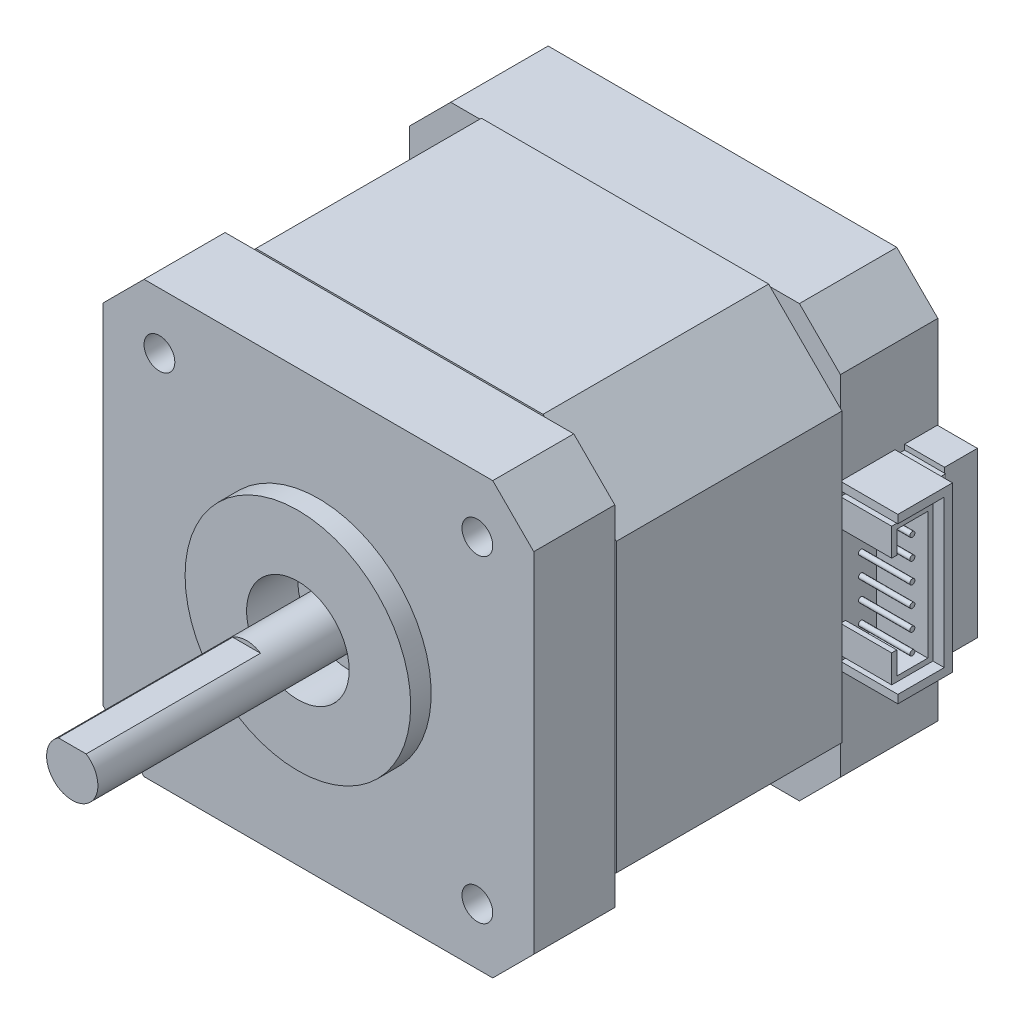
SolidWorks part; units mm, degrees
ref_plane "Front Plane" through (0, 0, 0) normal (0, 0, 1) x (1, 0, 0)
ref_plane "Top Plane" through (0, 0, 0) normal (0, 1, 0) x (1, 0, 0)
ref_plane "Right Plane" through (0, 0, 0) normal (1, 0, 0) x (0, 0, -1)
sketch "Sketch1" plane through (0, 0, 0) normal (0, 0, 1) x (1, 0, 0)
  line L0 (-17, 21) -> (-21, 17)
  line L1 (-17, -21) -> (17, -21)
  line L2 (-21, -17) -> (-21, 17)
  line L3 (-17, 21) -> (17, 21)
  line L4 (21, -17) -> (21, 17)
  line L5 (21, 17) -> (17, 21)
  line L6 (17, -21) -> (21, -17)
  line L12 (-21, -17) -> (-17, -21)
  point P0 (0, 0)
  point P15 (0, 0)
  dimension "D1" = 4
extrude "Boss-Extrude1" add sketch "Sketch1" along normal blind 9.5
sketch "Sketch2" plane through (0, 0, 9.5) normal (0, 0, 1) x (1, 0, 0)
  line L0 (14, 21.15) -> (21.15, 14)
  line L5 (-14, -21.15) -> (14, -21.15)
  line L6 (-21.15, -14) -> (-21.15, 14)
  line L7 (-14, 21.15) -> (14, 21.15)
  line L12 (21.15, -14) -> (21.15, 14)
  line L14 (17.5, -17.5) -> (17.575, -17.575) construction
  line L15 (-21.15, 14) -> (-14, 21.15)
  line L16 (21.15, -14) -> (14, -21.15)
  line L17 (-14, -21.15) -> (-21.15, -14)
  line L18 (17.5, 17.5) -> (17.575, 17.575) construction
  point P0 (0, 0)
  point P1 (0, 0)
  point P13 (0, 0)
  point P16 (0, 0)
  point P19 (0, 0)
  point P22 (0, 0)
  point P29 (0, 0)
  dimension "D1" = 4
  dimension "D5" = 4
extrude "Boss-Extrude2" add sketch "Sketch2" along normal blind 22
sketch "Sketch3" plane through (0, 0, 31.5) normal (0, 0, 1) x (1, 0, 0)
  line L0 (-17, 21) -> (17, 21)
  line L1 (17, 21) -> (21, 17)
  line L2 (21, 17) -> (21, -17)
  line L3 (21, -17) -> (17, -21)
  line L4 (17, -21) -> (-17, -21)
  line L5 (-17, -21) -> (-21, -17)
  line L6 (-21, -17) -> (-21, 17)
  line L7 (-21, 17) -> (-17, 21)
extrude "Boss-Extrude3" add sketch "Sketch3" along normal blind 7.9
sketch "Sketch5" plane through (0, 0, 39.4) normal (0, 0, 1) x (1, 0, 0)
  circle A0 centre (0, 0) radius 11
  circle A1 centre (0, 0) radius 5
  dimension "D1" = 22
  dimension "D2" = 10
extrude "Boss-Extrude4" add sketch "Sketch5" along normal blind 2
sketch "Sketch6" plane through (0, 0, 39.4) normal (0, 0, 1) x (1, 0, 0)
  circle A0 centre (0, 0) radius 5
extrude "Cut-Extrude1" cut sketch "Sketch6" against normal blind 3
sketch "Sketch7" plane through (0, 0, 36.4) normal (0, 0, 1) x (1, 0, 0)
  circle A0 centre (0, 0) radius 2.5
  dimension "D1" = 5
extrude "Boss-Extrude5" add sketch "Sketch7" along normal up to surface (5 mm away) up to face at (11, 0, 41.4)
sketch "Sketch8" plane through (0, 0, 41.4) normal (0, 0, 1) x (1, 0, 0)
  circle A0 centre (0, 0) radius 2.5
extrude "Boss-Extrude6" add sketch "Sketch8" along normal blind 22
sketch "Sketch9" plane through (0, 0, 63.4) normal (0, 0, 1) x (1, 0, 0)
  line L0 (-2.3166, 2.1) -> (3.6979, 2.1)
  line L1 (3.6979, 2.1) -> (-0.1236, 3.991)
  line L2 (-0.1236, 3.991) -> (-2.3166, 2.1)
extrude "Cut-Extrude2" cut sketch "Sketch9" against normal blind 17
sketch "Sketch10" plane through (0, 21.15, 0) normal (0, 1, 0) x (1, 0, 0)
  line L1 (-13, -13.6909) -> (13, -13.6909)
  line L3 (-13, -27.8113) -> (13, -27.8113)
  line L6 (-13, -13.6909) -> (-13, -27.8113)
  line L8 (13, -13.6909) -> (13, -27.8113)
extrude "Boss-Extrude7" [suppressed] add sketch "Sketch10" along normal blind 0.01
sketch "Sketch11" plane through (21, 0, 0) normal (1, 0, 0) x (0, 0, -1)
  line L1 (-3.2456, -8) -> (-0.0456, -8)
  line L3 (-3.2456, 8) -> (-0.0456, 8)
  line L5 (-3.2456, 8) -> (-3.2456, -8)
  line L7 (-0.0456, 8) -> (-0.0456, -8)
  point P0 (0, 0)
  dimension "D2" = 3.2
extrude "Boss-Extrude8" add sketch "Sketch11" along normal blind 3.9
sketch "Sketch12" plane through (21, 0, 0) normal (1, 0, 0) x (0, 0, -1)
  line L0 (-9.5, -14.15) -> (-9.5, 14.15) construction
  line L2 (-9.5, 7.479) -> (-9.5, 7.2)
  line L5 (-0.0456, 8) -> (-3.2456, 8) construction
  line L6 (-9.5, 7.2) -> (-4.9761, 7.2)
  line L9 (-4.1761, 7.2) -> (-4.1761, -7.2)
  line L10 (-4.1761, 8) -> (-9.5, 8)
  line L11 (-9.5, -14) -> (-9.5, 14) construction
  line L12 (-9.5, 7.479) -> (-9.5, 7.2)
  line L13 (-0.0456, 0) -> (6.3047, 0) construction
  line L14 (-0.0456, -8) -> (-0.0456, 8) construction
  line L15 (-9.5, -7.2) -> (-4.9761, -7.2)
  line L16 (-9.5, 7.2) -> (-9.5, 8)
  line L17 (-9.5, -7.2) -> (-9.5, -8)
  line L19 (-4.1761, -8) -> (-9.5, -8)
  line L20 (-4.9761, 7.2) -> (-4.9761, -7.2)
  line L21 (-4.1761, 8) -> (-4.1761, 7.2)
  line L22 (-4.1761, -7.2) -> (-4.1761, -8)
  dimension "D1" = 0.8
  dimension "D2" = 0.8
extrude "Boss-Extrude9" add sketch "Sketch12" along normal blind 5.6 contours L16 L10 L21 L9 L22 L19 L17 L15 L20 L6
sketch "Sketch13" plane through (21, 0, 0) normal (1, 0, 0) x (0, 0, -1)
  line L0 (-4.1761, 8) -> (-4.1761, -8) construction
  line L1 (-4.1761, 7.5) -> (-3.2456, 7.5)
  line L2 (-4.1761, 7.5) -> (-4.1761, -7.5)
  line L3 (-4.1761, -7.5) -> (-3.2456, -7.5)
  line L4 (-3.2456, 7.5) -> (-3.2456, -7.5)
  line L5 (-3.2456, 8) -> (-3.2456, -8) construction
  line L6 (-0.0456, 8) -> (-3.2456, 8) construction
  line L7 (-3.2456, -8) -> (-0.0456, -8) construction
  dimension "D1" = 0.5
  dimension "D2" = 0.5
extrude "Boss-Extrude10" add sketch "Sketch13" along normal up to surface (3.9 mm away) up to face at (24.9, 0, 1.6456)
sketch "Sketch14" plane through (24.9, 0, 0) normal (1, 0, 0) x (0, 0, -1)
  line L1 (-4.1761, 7.5) -> (-3.2456, 7.5)
  line L2 (-4.1761, 7.5) -> (-4.1761, -7.5)
  line L3 (-4.1761, -7.5) -> (-3.2456, -7.5)
  line L4 (-3.2456, 7.5) -> (-3.2456, -7.5)
extrude "Boss-Extrude11" add sketch "Sketch14" along normal blind 0.1
sketch "Sketch15" plane through (21, 0, 0) normal (1, 0, 0) x (0, 0, -1)
  line L0 (-5.9761, 6.2) -> (-9, 6.2)
  line L5 (0, 0) -> (5.9447, 0) construction
  line L6 (-9.5, -7.2) -> (-9.5, 7.2) construction
  line L7 (-9.5, 4) -> (-9, 4)
  line L9 (-9.5, -4) -> (-9, -4)
  line L11 (-9.5, 7.2) -> (-4.9761, 7.2) construction
  line L12 (-9, 6.7) -> (-5.4761, 6.7)
  line L13 (-9, 6.2) -> (-9, 4)
  line L14 (-9, -6.7) -> (-5.4761, -6.7)
  line L15 (-5.4761, 6.7) -> (-5.4761, -6.7)
  line L16 (-4.9761, 7.2) -> (-4.9761, -7.2) construction
  line L17 (-9, 6.7) -> (-9.5, 6.7)
  line L18 (-9.5, -7.2) -> (-9.5, 7.2) construction
  line L19 (-9.5, 6.7) -> (-9.5, 4)
  line L20 (-5.9761, 6.2) -> (-5.9761, -6.2)
  line L21 (-9.5, -7.2) -> (-4.9761, -7.2) construction
  line L22 (-9, -6.2) -> (-5.9761, -6.2)
  line L23 (-9.5, -4) -> (-9.5, -6.7)
  line L24 (-9.5, -6.7) -> (-9, -6.7)
  line L25 (-9, -4) -> (-9, -6.2)
  dimension "D1" = 4
  dimension "D2" = 4
  dimension "D4" = 0.5
  dimension "D5" = 0.5
  dimension "D6" = 0.5
  dimension "D7" = 0.5
  dimension "D8" = 0.5
  dimension "D9" = 0.5
extrude "Boss-Extrude12" add sketch "Sketch15" along normal blind 5
sketch "Sketch16" plane through (21, 0, 0) normal (1, 0, 0) x (0, 0, -1)
  line L0 (-7.4881, 6.2) -> (-7.4881, 5) construction
  line L1 (-9, 6.2) -> (-5.9761, 6.2) construction
  circle A0 centre (-7.4881, 5) radius 0.25
  circle A1 centre (-7.4881, 3) radius 0.25
  circle A2 centre (-7.4881, 1) radius 0.25
  circle A3 centre (-7.4881, -1) radius 0.25
  circle A4 centre (-7.4881, -3) radius 0.25
  circle A5 centre (-7.4881, -5) radius 0.25
  dimension "D2" = 0.5
  dimension "D1" = 1.2
  dimension "D3" = 6
extrude "Boss-Extrude13" add sketch "Sketch16" along normal blind 5
sketch "Sketch17" plane through (0, 0, 39.4) normal (0, 0, 1) x (1, 0, 0)
  circle A0 centre (-15.5, 15.5) radius 1.5
  circle A1 centre (15.5, 15.5) radius 1.5
  circle A2 centre (15.5, -15.5) radius 1.5
  circle A3 centre (-15.5, -15.5) radius 1.5
  point P0 (0, 0)
  point P13 (0, 0)
  dimension "D3" = 3
  dimension "D1" = 4
extrude "Cut-Extrude3" cut sketch "Sketch17" against normal blind 5.5
sketch "Sketch18" plane through (0, 0, 0) normal (0, 0, -1) x (-1, 0, 0)
  circle A0 centre (-15.5, 15.5) radius 3.25
  circle A1 centre (15.5, 15.5) radius 3.25
  circle A2 centre (15.5, -15.5) radius 3.25
  circle A3 centre (-15.5, -15.5) radius 3.25
  point P0 (0, 0)
  point P13 (0, 0)
  dimension "D3" = 6.5
  dimension "D1" = 4
extrude "Cut-Extrude4" cut sketch "Sketch18" against normal blind 3
sketch "Sketch20" plane through (0, 0, 3) normal (0, 0, -1) x (-1, 0, 0)
  circle A0 centre (-15.5, 15.5) radius 1.5
  circle A1 centre (15.5, 15.5) radius 1.5
  circle A2 centre (-15.5, -15.5) radius 1.5
  circle A3 centre (15.5, -15.5) radius 1.5
  dimension "D1" = 3
  dimension "D2" = 3
  dimension "D3" = 3
  dimension "D4" = 3
extrude "Cut-Extrude5" cut sketch "Sketch20" against normal blind 4
sketch "Sketch21" plane through (0, 0, 0) normal (0, 0, -1) x (-1, 0, 0)
  circle A0 centre (0, 0) radius 4.5
  dimension "D1" = 9
extrude "Cut-Extrude6" cut sketch "Sketch21" against normal blind 4
